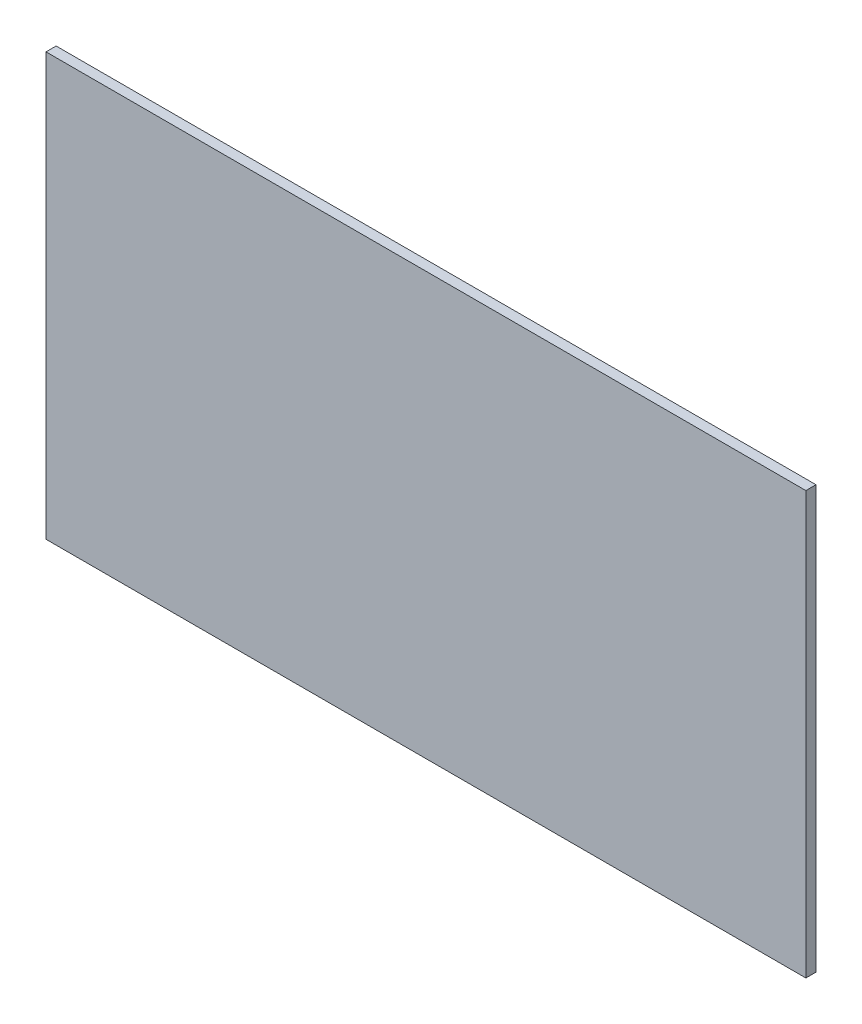
SolidWorks part; units mm, degrees
ref_plane "前视基准面" through (0, 0, 0) normal (0, 0, 1) x (1, 0, 0)
ref_plane "上视基准面" through (0, 0, 0) normal (0, 1, 0) x (1, 0, 0)
ref_plane "右视基准面" through (0, 0, 0) normal (1, 0, 0) x (0, 0, -1)
sketch "草图1" plane through (0, 0, 0) normal (0, 0, 1) x (1, 0, 0)
  line L0 (-45, -25) -> (45, -25)
  line L1 (45, -25) -> (45, 25)
  line L2 (45, 25) -> (-45, 25)
  line L3 (-45, 25) -> (-45, -25)
base flange "基体-法兰1" sketch "草图1" thickness 1.2 reverse thickness direction no parameters "D1"=1.2
sketch "折弯-线1" [suppressed] plane through (0, 0, 0) normal (0, 1, 0) x (1, 0, 0)
sketch "边界框1" [suppressed] plane through (0, 0, 0) normal (0, 1, 0) x (1, 0, 0)
sheet metal parameters "钣金2" thickness 1.2 parameters "D1"=1.2
flat pattern "平板型式2" [suppressed]
sketch "折弯-线2" plane through (0, 0, 0) normal (0, 1, 0) x (1, 0, 0)
sketch3d "边界框2" [suppressed]
  line L0 (45, -25, 0) -> (-45, -25, 0) construction
  line L1 (45, 25, 0) -> (-45, 25, 0) construction
  line L2 (45, -25, 0) -> (45, 25, 0) construction
  line L3 (-45, -25, 0) -> (-45, 25, 0) construction
